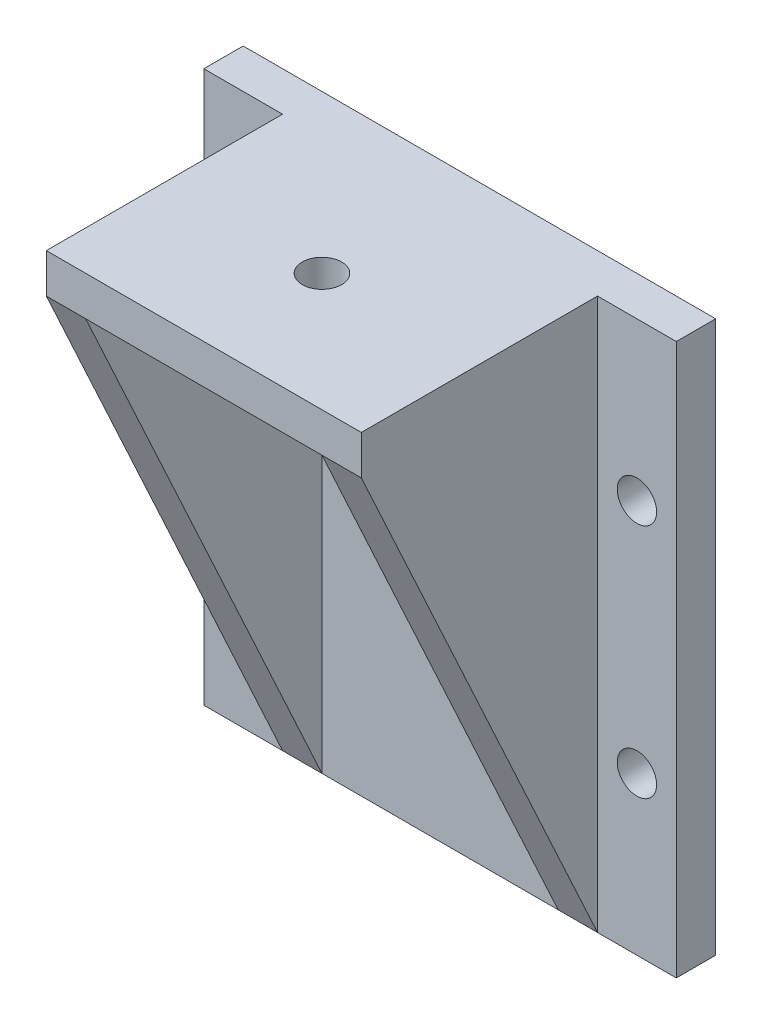
SolidWorks part; units mm, degrees
ref_plane "Plan de face" through (0, 0, 0) normal (0, 0, 1) x (1, 0, 0)
ref_plane "Plan de dessus" through (0, 0, 0) normal (0, 1, 0) x (1, 0, 0)
ref_plane "Plan de droite" through (0, 0, 0) normal (1, 0, 0) x (0, 0, -1)
sketch "Esquisse1" plane through (0, 0, 0) normal (0, 0, 1) x (1, 0, 0)
  line L1 (-36.7149, 33.2769) -> (23.2851, 33.2769)
  line L2 (-36.7149, 33.2769) -> (-36.7149, -36.7231)
  line L3 (-36.7149, -36.7231) -> (23.2851, -36.7231)
  line L4 (23.2851, 33.2769) -> (23.2851, -36.7231)
  dimension "D1" = 70
  dimension "D2" = 60
extrude "Boss.-Extru.1" add sketch "Esquisse1" along normal blind 5
sketch "Esquisse3" plane through (0, 0, 5) normal (0, 0, 1) x (1, 0, 0)
  line L0 (-26.7149, -36.7231) -> (-26.7149, 33.2769)
  line L1 (-36.7149, -36.7231) -> (23.2851, -36.7231) construction
  line L2 (23.2851, 33.2769) -> (-36.7149, 33.2769) construction
  line L3 (-26.7149, 33.2769) -> (13.2851, 33.2769)
  line L4 (13.2851, 33.2769) -> (13.2851, -36.7231)
  line L5 (13.2851, -36.7231) -> (8.2851, -36.7231)
  line L6 (8.2851, -36.7231) -> (8.2851, 28.2769)
  line L7 (8.2851, 28.2769) -> (-21.7149, 28.2769)
  line L8 (-21.7149, 28.2769) -> (-21.7149, -36.7231)
  line L9 (-21.7149, -36.7231) -> (-26.7149, -36.7231)
  line L10 (-36.7149, 33.2769) -> (-36.7149, -36.7231) construction
  line L11 (23.2851, -36.7231) -> (23.2851, 33.2769) construction
  dimension "D1" = 5
  dimension "D2" = 10
  dimension "D3" = 10
  dimension "D4" = 5
  dimension "D5" = 5
extrude "Boss.-Extru.2" add sketch "Esquisse3" along normal blind 30
sketch "Esquisse4" plane through (-26.7149, 0, 0) normal (-1, 0, 0) x (0, 0, 1)
  line L0 (35, 28.2769) -> (5, -36.7231)
  line L1 (35, 33.2769) -> (35, -36.7231) construction
  line L2 (35, -36.7231) -> (5, -36.7231) construction
  line L3 (5, -36.7231) -> (35, -36.7231)
  line L4 (35, -36.7231) -> (35, 28.2769)
  dimension "D1" = 5
extrude "Enlèv. mat.-Extru.1" cut sketch "Esquisse4" against normal up to surface (40 mm away) up to face at (13.2851, -10.4731, 27.5)
sketch "Esquisse5" plane through (0, 0, 5) normal (0, 0, 1) x (1, 0, 0)
  line L0 (-36.7149, 33.2769) -> (-36.7149, -36.7231) construction
  line L1 (-26.7149, 33.2769) -> (-36.7149, 33.2769) construction
  line L2 (-36.7149, -36.7231) -> (-26.7149, -36.7231) construction
  line L3 (23.2851, -36.7231) -> (23.2851, 33.2769) construction
  circle A0 centre (-31.7149, 13.2769) radius 2.5
  circle A1 centre (-31.7149, -16.7231) radius 2.5
  circle A2 centre (18.2851, -16.7231) radius 2.5
  circle A3 centre (18.2851, 13.2769) radius 2.5
  dimension "D1" = 5
  dimension "D4" = 5
  dimension "D7" = 5
  dimension "D9" = 5
  dimension "D2" = 5
  dimension "D3" = 20
  dimension "D5" = 5
  dimension "D6" = 20
  dimension "D8" = 5
extrude "Enlèv. mat.-Extru.2" cut sketch "Esquisse5" against normal up to surface (5 mm away) up to face at (-6.7149, -1.7231, 0)
sketch "Esquisse6" plane through (0, 28.2769, 0) normal (0, -1, 0) x (1, 0, 0)
  line L0 (-21.7149, 35) -> (8.2851, 35) construction
  line L3 (-21.7149, 35) -> (-21.7149, 5) construction
  circle A0 centre (-6.7149, 20) radius 13
  point P6 (8.2851, 17.3525)
  dimension "D1" = 26
  dimension "D2" = 15
  dimension "D3" = 15
extrude "Enlèv. mat.-Extru.3" cut sketch "Esquisse6" against normal blind 1
sketch "Esquisse7" plane through (0, 29.2769, 0) normal (0, -1, 0) x (1, 0, 0)
  line L0 (13.2851, 35) -> (-26.7149, 35) construction
  line L1 (-21.7149, 35) -> (-21.7149, 5) construction
  circle A0 centre (-6.7149, 20) radius 2.5
  point P2 (-6.7149, 35)
  dimension "D3" = 5
  dimension "D1" = 15
  dimension "D2" = 15
extrude "Enlèv. mat.-Extru.4" cut sketch "Esquisse7" against normal up to surface (4 mm away) up to face at (-5.4649, 33.2769, 15)
